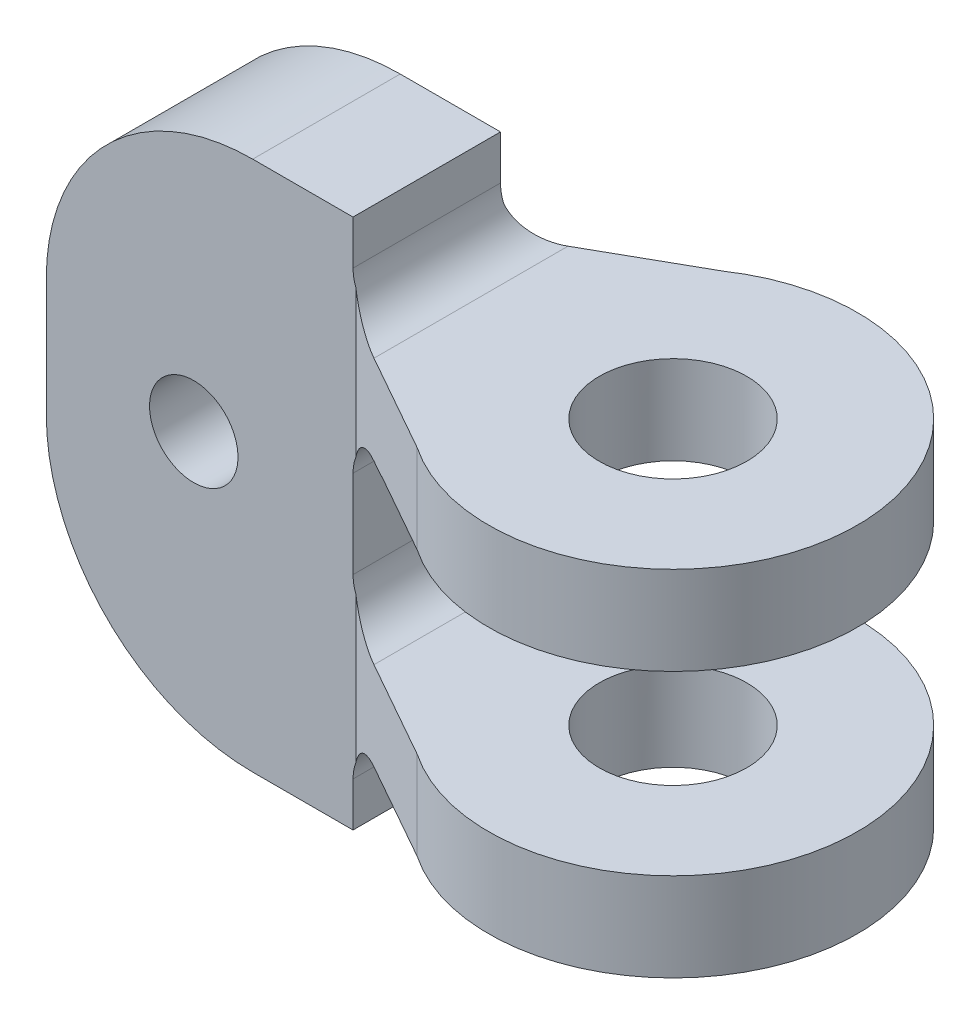
SolidWorks part; units mm, degrees
ref_plane "Alzado" through (0, 0, 0) normal (0, 0, 1) x (1, 0, 0)
ref_plane "Planta" through (0, 0, 0) normal (0, 1, 0) x (1, 0, 0)
ref_plane "Vista lateral" through (0, 0, 0) normal (1, 0, 0) x (0, 0, -1)
sketch "Croquis1" plane through (0, 0, 0) normal (0, 0, 1) x (1, 0, 0)
  line L0 (11.25, 17.1) -> (11.25, 14.1)
  line L1 (5.75, -0.9) -> (11.25, -0.9)
  line L2 (-1.25, 6.1) -> (-1.25, 10.1)
  line L3 (5.75, 17.1) -> (11.25, 17.1)
  line L4 (11.25, 11.1) -> (23.75, 11.1)
  line L5 (-1.25, -0.9) -> (1.25, 0.9) construction
  line L6 (-1.25, 17.1) -> (-1.0254, 14.0276) construction
  line L7 (11.25, 11.1) -> (11.25, 5.1)
  line L8 (-1.25, 8.1) -> (23.75, 8.1) construction
  line L9 (23.75, 5.1) -> (11.25, 5.1)
  line L10 (11.25, 2.1) -> (11.25, -0.9)
  line L11 (23.75, 11.1) -> (23.75, 14.1)
  line L12 (23.75, 14.1) -> (11.25, 14.1)
  line L13 (11.25, 17.1) -> (-1.25, 17.1) construction
  line L14 (23.75, 5.1) -> (23.75, 2.1)
  line L15 (23.75, 2.1) -> (11.25, 2.1)
  circle A0 centre (3.75, 8.1) radius 1.5
  arc A1 (-1.25, 10.1) -> (5.75, 17.1) centre (5.75, 10.1) cw
  arc A2 (5.75, -0.9) -> (-1.25, 6.1) centre (5.75, 6.1) cw
  point P0 (0, 0)
  dimension "D6" = 3
  dimension "D4" = 7
  dimension "D2" = 18
  dimension "D3" = 12.5
  dimension "D7" = 5
  dimension "D8" = 9
  dimension "D10" = 3
  dimension "D11" = 3
extrude "Saliente-Extruir1" add sketch "Croquis1" along normal blind 15
sketch "Croquis2" plane through (0, 0, 0) normal (0, 1, 0) x (1, 0, 0)
  line L0 (23.75, -7.5) -> (11.25, -7.5) construction
  line L1 (23.75, -7.5) -> (11.25, -7.5) construction
  line L2 (23.75, -15) -> (23.75, 0) construction
  line L3 (17.5, -1.25) -> (11.25, 0)
  line L4 (17.5, -13.75) -> (11.25, -15)
  line L5 (11.25, -15) -> (11.25, -17.9613)
  line L6 (11.25, -17.9613) -> (29.6635, -17.9613)
  line L7 (29.6635, -17.9613) -> (29.6635, 1.8686)
  line L8 (29.6635, 1.8686) -> (11.1263, 1.8686)
  line L9 (11.1263, 1.8686) -> (11.25, 0)
  line L10 (11.25, -15) -> (11.25, 0) construction
  line L11 (17.5, 0) -> (17.5, -15) construction
  line L12 (23.75, 0) -> (11.25, 0) construction
  line L13 (23.75, -15) -> (11.25, -15) construction
  circle A0 centre (17.5, -7.5) radius 2.5
  arc A1 (17.5, -13.75) -> (17.5, -1.25) centre (17.5, -7.5) ccw
  dimension "D1" = 5
extrude "Cortar-Extruir1" cut sketch "Croquis2" along normal blind 20
sketch "Croquis4" plane through (0, 17.1, 0) normal (0, 1, 0) x (1, 0, 0)
  line L0 (17.5, -1.25) -> (17.5, -13.75) construction
  line L1 (-1.25, -15) -> (-1.25, 0) construction
  line L2 (-4.3896, -10) -> (9.25, -10)
  line L3 (9.25, -5) -> (14.0073, -2.317)
  line L4 (-4.3896, -5) -> (9.25, -5)
  line L5 (17.5, -1.25) -> (17.5, 1.8877)
  line L6 (17.5, -7.5) -> (9.25, -7.5) construction
  line L7 (9.25, -10) -> (14.0073, -12.683)
  line L11 (17.5, 1.8877) -> (-4.3896, 1.8877)
  line L12 (-4.3896, 1.8877) -> (-4.3896, -5)
  line L13 (-4.3896, -10) -> (-4.3896, -16.4565)
  line L14 (-4.3896, -16.4565) -> (17.5, -16.4565)
  line L15 (17.5, -16.4565) -> (17.5, -13.75)
  arc A0 (14.0073, -12.683) -> (17.5, -13.75) centre (17.5, -7.5) ccw
  arc A1 (17.5, -1.25) -> (14.0073, -2.317) centre (17.5, -7.5) ccw
  point P6 (-1.25, -7.5)
extrude "Cortar-Extruir2" cut sketch "Croquis4" against normal blind 26
ref_plane "Plano1" through (0, 0, 7.5) normal (0, 0, 1) x (1, 0, 0)
sketch "Croquis5" plane through (0, 0, 10) normal (0, 0, 1) x (1, 0, 0)
  line L3 (14.0073, 14.1) -> (11.25, 14.1) construction
  line L4 (13.1219, 14.1) -> (9.15, 14.1)
  line L5 (13.1219, 14.1) -> (13.1219, 17.4957)
  line L6 (13.1219, 17.4957) -> (9.15, 17.4957)
  line L7 (9.15, 14.1) -> (9.15, 17.4957)
  line L8 (14.0073, 5.1) -> (11.25, 5.1) construction
  line L9 (13.4339, 5.1) -> (9.15, 5.1)
  line L10 (13.4339, 5.1) -> (13.4339, 11.0777)
  line L11 (13.4339, 11.0777) -> (9.15, 11.0777)
  line L12 (9.15, 5.1) -> (9.15, 11.0777)
  line L13 (11.25, 2.1) -> (14.0073, 2.1) construction
  line L14 (13.6515, 2.1) -> (9.15, 2.1)
  line L15 (13.6515, 2.1) -> (13.6515, -1.8918)
  line L16 (13.6515, -1.8918) -> (9.15, -1.8918)
  line L17 (9.15, 2.1) -> (9.15, -1.8918)
  line L18 (11.25, 14.1) -> (11.25, 17.1) construction
  line L19 (11.25, 5.1) -> (11.25, 11.1) construction
  line L20 (11.25, -0.9) -> (11.25, 2.1) construction
  dimension "D1" = 2.1
  dimension "D2" = 2.1
  dimension "D3" = 2.1
extrude "Cortar-Extruir5" cut sketch "Croquis5" against normal mid plane 20
fillet "Redondeo1" radius 1.5 4 edges at (9.15, 2.1, 7.5) (9.15, 5.1, 7.5) (9.15, 11.0777, 7.5) (9.15, 14.1, 7.5)
